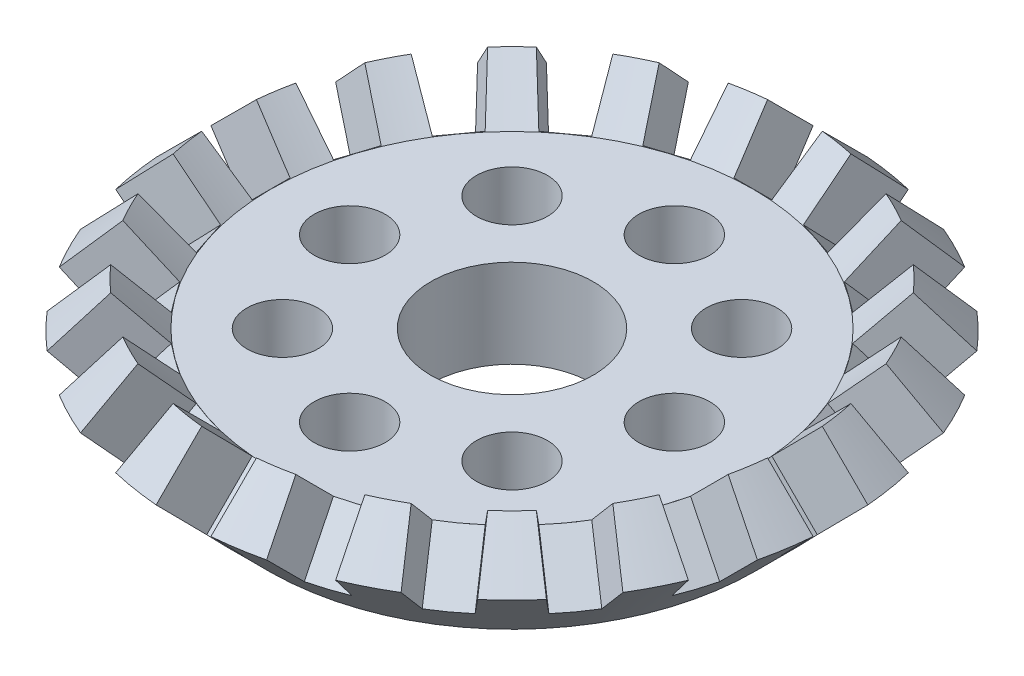
SolidWorks part; units mm, degrees
ref_plane "Front Plane" through (0, 0, 0) normal (0, 0, 1) x (1, 0, 0)
ref_plane "Top Plane" through (0, 0, 0) normal (0, 1, 0) x (1, 0, 0)
ref_plane "Right Plane" through (0, 0, 0) normal (1, 0, 0) x (0, 0, -1)
sketch "Sketch2" plane through (0, 0, 0) normal (0, 0, 1) x (1, 0, 0)
  line L6 (0, 0) -> (0, 4.3558)
  line L7 (0, 0) -> (-12, 0)
  line L9 (-12, 0) -> (-16.2426, 4.2426)
  line L14 (-16.2426, 4.2426) -> (-14.0081, 6.4771)
  line L15 (-11.8868, 4.3558) -> (-14.0081, 6.4771)
  line L16 (-11.8868, 4.3558) -> (0, 4.3558)
  dimension "D2" = 12
  dimension "D4" = 45
  dimension "D5" = 6
  dimension "D6" = 3
revolve "Revolve4" add sketch "Sketch2" angle 360 about L6
sketch "Sketch3" plane through (0, 0, 0) normal (0, 0, 1) x (1, 0, 0)
  line L0 (0, 0) -> (0, 20.4853) construction
  line L1 (0, 20.4853) -> (0, -16.6359) construction
  line L2 (0, 20.4853) -> (-22.6315, -2.1462) construction
  line L3 (-14.0081, 6.4771) -> (-16.2426, 4.2426) construction
ref_plane "Plane1" through (-6, -6, 0) normal (-0.7071, -0.7071, 0) x (0, 0, 1)
sketch "Sketch4" plane through (-6, -6, 0) normal (-0.7071, -0.7071, 0) x (0, 0, 1)
  line L0 (0, 9.4379) -> (0, 20.3385) construction
  line L1 (0, 0) -> (0, 14.4853) construction
  line L8 (-0.9337, 11.4896) -> (0.9337, 11.4896)
  line L9 (0.9337, 11.4896) -> (1.4119, 14.8882)
  line L10 (1.4119, 14.8882) -> (-1.4119, 14.8882)
  line L11 (-0.9337, 11.4896) -> (-1.4119, 14.8882)
  point P9 (0.8189, 11.5148)
  point P10 (0, 11.4896)
  point P11 (0, 14.0042)
  point P12 (0, 14.8882)
  point P13 (0, 17.9558)
  point P14 (0, 14.0042)
  point P15 (0, 17.9558)
  point P16 (0.9337, 11.4896)
extrude "Cut-Extrude11" cut sketch "Sketch4" against normal blind 10 contours L10 L11 L8 L9
sketch "Sketch5" plane through (0, 4.3558, 0) normal (0, 1, 0) x (1, 0, 0)
  line L0 (0, 0) -> (0, -8)
  circle A0 centre (0, 0) radius 4
  circle A1 centre (0, -8) radius 1.75
  dimension "D1" = 8
  dimension "D3" = 3.5
  dimension "D2" = 8
extrude "Cut-Extrude12" cut sketch "Sketch5" against normal blind 10 contours A0 region at (-2.7484, 4.3558, -2.7484)
extrude "Cut-Extrude13" cut sketch "Sketch5<3>" against normal blind 10 contours A1
sketch "Sketch5<3>" plane through (0, 4.3558, 0) normal (0, 1, 0) x (1, 0, 0) same geometry as "Sketch5"
pattern_circular "CirPattern13" count 8 over 360 about axis through (0, 20.4853, 0) along (0, -1, 0) of "Cut-Extrude13"
pattern_circular "CirPattern14" count 20 over 360 about axis through (0, 0, 0) along (0, 1, 0) of "Cut-Extrude11" reverse direction yes
